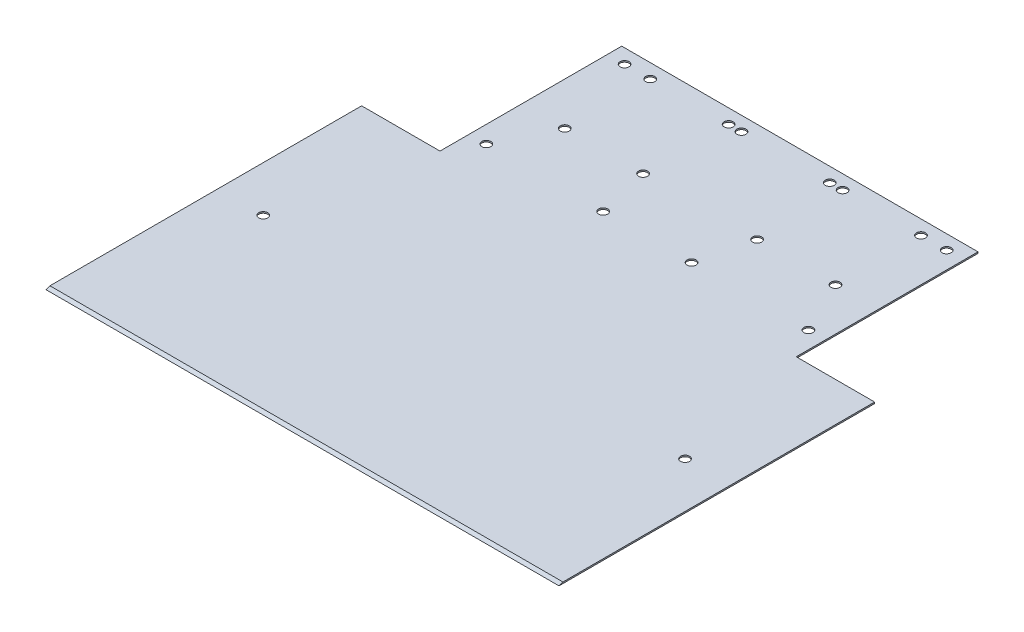
SolidWorks part; units mm, degrees
ref_plane "Alzado" through (0, 0, 0) normal (0, 0, 1) x (1, 0, 0)
ref_plane "Planta" through (0, 0, 0) normal (0, 1, 0) x (1, 0, 0)
ref_plane "Vista lateral" through (0, 0, 0) normal (1, 0, 0) x (0, 0, -1)
sketch "Croquis2" plane through (0, 0, 0) normal (0, 1, 0) x (1, 0, 0)
  line L0 (-90, 25.54) -> (-62.5, 25.54)
  line L1 (90, -85.2) -> (-90, -85.2)
  line L2 (90, -85.2) -> (90, 25.54)
  line L3 (62.5, 89.31) -> (-62.5, 89.31)
  line L4 (-90, -85.2) -> (-90, 25.54)
  line L5 (90, -85.2) -> (-62.5, 59.1667) construction
  line L6 (62.5, 59.1667) -> (-90, -85.2) construction
  line L7 (-62.5, 25.54) -> (-62.5, 89.31)
  line L8 (0, 4.11) -> (0, 89.31) construction
  line L9 (90, 25.54) -> (62.5, 25.54)
  line L10 (62.5, 25.54) -> (62.5, 89.31)
  point P0 (0, 0)
  dimension "D1" = 125
  dimension "D2" = 180
  dimension "D3" = 110.74
  dimension "D4" = 63.77
extrude "Saliente-Extruir1" add sketch "Croquis2" along normal blind 0.5
sketch "Croquis3" plane through (90, 0, 0) normal (1, 0, 0) x (0, 0, -1)
  line L0 (-85.2, 0) -> (-83.8263, 0.5)
  line L1 (-85.2, 0.5) -> (25.54, 0.5) construction
  line L2 (-83.8263, 0.5) -> (-85.2, 0.5)
  line L3 (-85.2, 0.5) -> (-85.2, 0)
  dimension "D1" = 70
sketch "Croquis5" plane through (0, 0.5, 0) normal (0, 1, 0) x (1, 0, 0)
  circle A0 centre (74, -24.9699) radius 1.585
sketch "Croquis6" plane through (0, 0.5, 0) normal (0, 1, 0) x (1, 0, 0)
  circle A0 centre (-56.5, 35.81) radius 1.585
  circle A1 centre (-15.5, 35.81) radius 1.585
  circle A2 centre (-15.5, 84.31) radius 1.585
  circle A3 centre (-56.5, 84.31) radius 1.585
extrude "Cortar-Extruir4" cut sketch "Croquis6" against normal up to next
sketch "Croquis7" plane through (0, 0.5, 0) normal (0, 1, 0) x (1, 0, 0)
  circle A0 centre (56.5, 35.81) radius 1.585
  circle A1 centre (15.5, 35.81) radius 1.585
  circle A2 centre (15.5, 84.31) radius 1.585
  circle A3 centre (56.5, 84.31) radius 1.585
extrude "Cortar-Extruir5" cut sketch "Croquis7" against normal up to next
mirror "Simetría3" about plane through (0, 0, 0) normal (1, 0, 0) of "Saliente-Extruir1"
sketch "Croquis8" plane through (0, 0.5, 0) normal (0, 1, 0) x (1, 0, 0)
  circle A0 centre (-20, 54.31) radius 1.585
  circle A1 centre (-47.5, 54.31) radius 1.585
  circle A2 centre (-47.5, 84.31) radius 1.585
  circle A3 centre (-20, 84.31) radius 1.585
extrude "Cortar-Extruir6" cut sketch "Croquis8" against normal up to next
mirror "Simetría4" about plane through (0, 0, 0) normal (1, 0, 0) of "Cortar-Extruir6"
sketch "Croquis9" plane through (0, 0, 0) normal (0, -1, 0) x (1, 0, 0)
  circle A0 centre (56.5, -35.81) radius 1.585
  circle A2 centre (15.5, -35.81) radius 1.585
  circle A3 centre (15.5, -84.31) radius 1.585
  circle A4 centre (56.5, -84.31) radius 1.585
extrude "Cortar-Extruir7" cut sketch "Croquis9" against normal up to next
mirror "Simetría5" about plane through (0, 0, 0) normal (1, 0, 0) of "Cortar-Extruir7"
extrude "Cortar-Extruir8" cut sketch "Croquis5" against normal up to next
mirror "Simetría6" about plane through (0, 0, 0) normal (1, 0, 0) of "Cortar-Extruir8"
extrude "Cortar-Extruir9" cut sketch "Croquis3" against normal up to next
